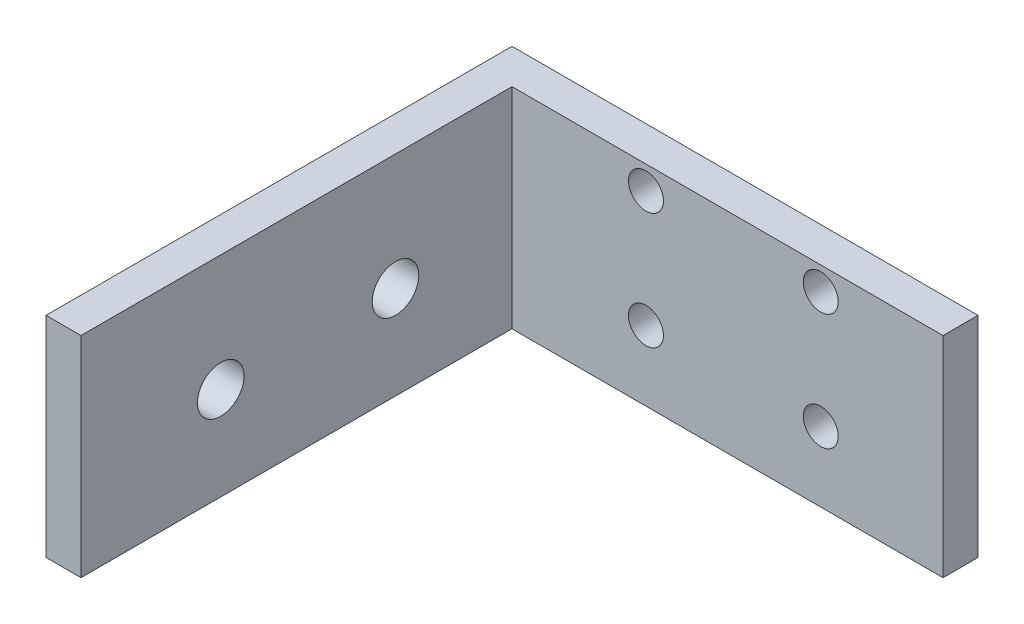
SolidWorks part; units mm, degrees
ref_plane "Plan de face" through (0, 0, 0) normal (0, 0, 1) x (1, 0, 0)
ref_plane "Plan de dessus" through (0, 0, 0) normal (0, 1, 0) x (1, 0, 0)
ref_plane "Plan de droite" through (0, 0, 0) normal (1, 0, 0) x (0, 0, -1)
sketch "Esquisse1" plane through (0, 0, 0) normal (0, 0, 1) x (1, 0, 0)
  line L1 (0, 0) -> (40, 0)
  line L2 (0, 0) -> (0, 18)
  line L3 (0, 18) -> (40, 18)
  line L4 (40, 0) -> (40, 18)
  dimension "D1" = 18
  dimension "D2" = 40
extrude "Boss.-Extru.1" add sketch "Esquisse1" along normal blind 3
sketch "Esquisse2" plane through (0, 0, 3) normal (0, 0, 1) x (1, 0, 0)
  line L0 (0, 0) -> (40, 0) construction
  line L1 (0, 18) -> (3, 18)
  line L2 (0, 18) -> (0, 0)
  line L3 (0, 0) -> (3, 0)
  line L4 (3, 18) -> (3, 0)
  dimension "D1" = 3
extrude "Boss.-Extru.2" add sketch "Esquisse2" along normal blind 37
sketch "Esquisse3" plane through (0, 0, 3) normal (0, 0, 1) x (1, 0, 0)
  line L0 (3, 0) -> (3, 18) construction
  line L4 (3, 0) -> (40, 0) construction
  circle A0 centre (14.5, 16) radius 1.5
  circle A1 centre (29.5, 16) radius 1.5
  circle A2 centre (14.5, 6) radius 1.5
  circle A3 centre (29.5, 6) radius 1.5
  dimension "D2" = 3
  dimension "D3" = 3
  dimension "D4" = 3
  dimension "D5" = 15
  dimension "D1" = 3
  dimension "D6" = 10
  dimension "D7" = 11.5
  dimension "D8" = 11.5
  dimension "D9" = 10
  dimension "D10" = 15
  dimension "D11" = 6
  dimension "D12" = 6
extrude "Enlèv. mat.-Extru.1" cut sketch "Esquisse3" against normal through all
sketch "Esquisse4" plane through (3, 0, 0) normal (1, 0, 0) x (0, 0, -1)
  line L0 (-40, 18) -> (-3, 18) construction
  line L1 (-3, 0) -> (-3, 18) construction
  circle A0 centre (-28, 8) radius 2
  circle A1 centre (-13, 8) radius 2
  dimension "D1" = 4
  dimension "D2" = 4
  dimension "D3" = 15
  dimension "D4" = 10
  dimension "D5" = 10
  dimension "D6" = 10
extrude "Enlèv. mat.-Extru.2" cut sketch "Esquisse4" against normal through all
